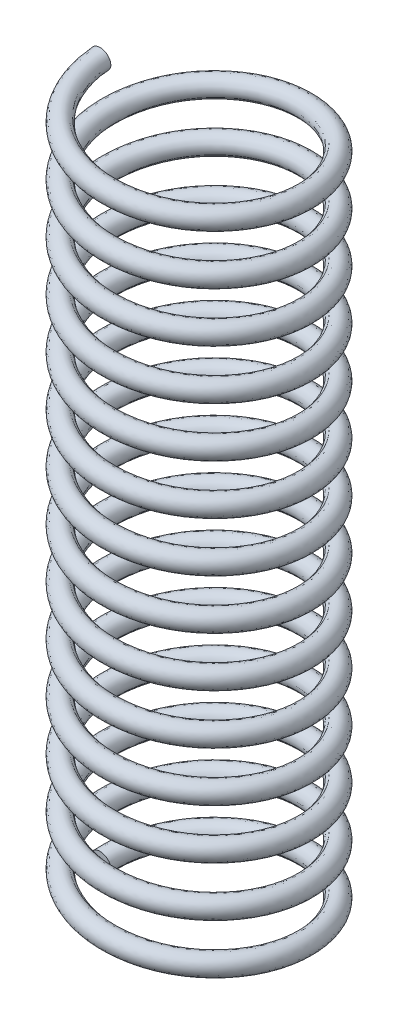
SolidWorks part; units mm, degrees
note: '?' marks a value the reader was unsure of.
material "Galvanized Steel"
ref_plane "Front Plane" through (0, 0, 0) normal (0, 0, 1) x (1, 0, 0)
ref_plane "Top Plane" through (0, 0, 0) normal (0, 1, 0) x (1, 0, 0)
ref_plane "Right Plane" through (0, 0, 0) normal (1, 0, 0) x (0, 0, -1)
ref_axis "X-axis" through (-88.99, 0, 0) along (1, 0, 0)?
ref_axis "Y-axis" through (0, 55, 0) along (0, -1, 0)?
ref_axis "Z-axis" through (0, 0, -88.99) along (0, 0, 1)?
sketch "Sketch1" plane through (0, 0, 0) normal (0, 1, 0) x (1, 0, 0)
  circle A0 centre (0, 0) radius 2.75
  dimension "D1" = 5.5
curve "Helix/Spiral1" pitch 1.3929 height 19.5 radius 2.75 left hand yes centre (0, 0, 0) axis (0, 1, 0) start towards (0, 0, 1)
sweep "Sweep1" add path "Helix/Spiral1" circular profile diameter 0.56 parameters "D3"=0.56
